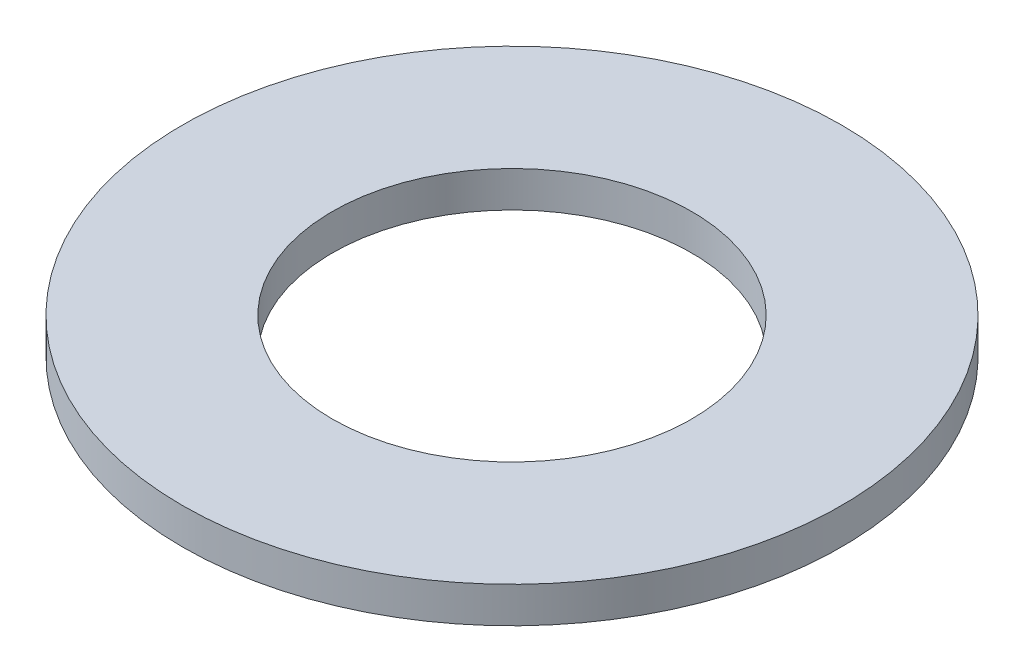
SolidWorks part; units mm, degrees
material "Caoutchouc silicone"
ref_plane "Plan de face" through (0, 0, 0) normal (0, 0, 1) x (1, 0, 0)
ref_plane "Plan de dessus" through (0, 0, 0) normal (0, 1, 0) x (1, 0, 0)
ref_plane "Plan de droite" through (0, 0, 0) normal (1, 0, 0) x (0, 0, -1)
sketch "Esquisse1" plane through (0, 0, 0) normal (0, 1, 0) x (1, 0, 0)
  circle A0 centre (0, 0) radius 5.5
  circle A1 centre (0, 0) radius 3
  dimension "D1" = 11
  dimension "D2" = 6
extrude "Boss.-Extru.1" add sketch "Esquisse1" along normal blind 0.6
